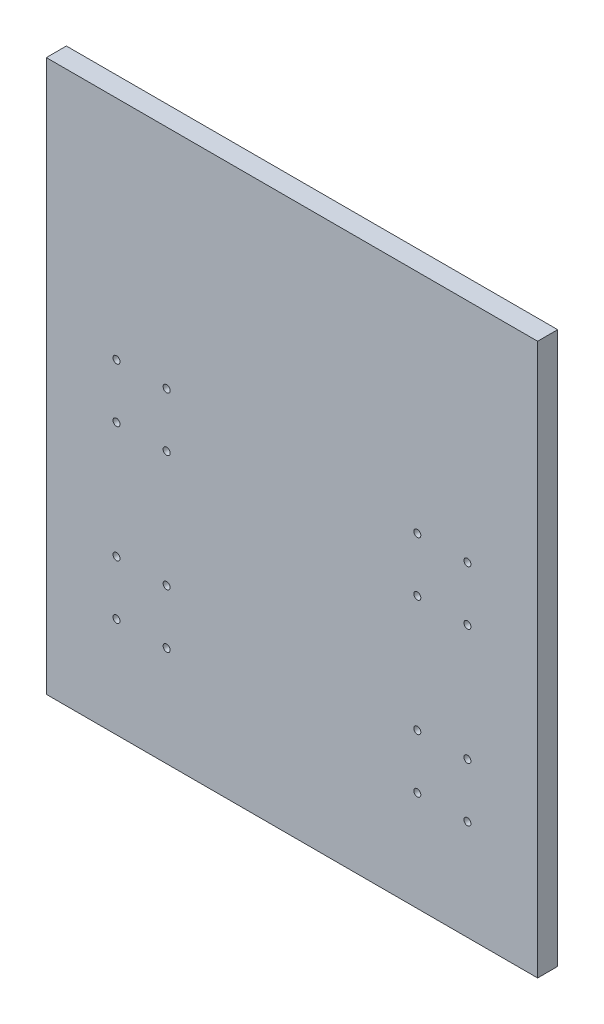
SolidWorks part; units mm, degrees
material "Органическое стекло СО-95-К ГОСТ 10667-90"
ref_plane "Спереди" through (0, 0, 0) normal (0, 0, 1) x (1, 0, 0)
ref_plane "Сверху" through (0, 0, 0) normal (0, 1, 0) x (1, 0, 0)
ref_plane "Справа" through (0, 0, 0) normal (1, 0, 0) x (0, 0, -1)
ref_axis "ОсьX" through (-88.99, 0, 0) along (1, 0, 0)
ref_axis "ОсьZ" through (0, 55, 0) along (0, -1, 0)
ref_axis "ОсьY" through (0, 0, -88.99) along (0, 0, 1)
sketch "Эскиз1" plane through (0, 0, 0) normal (0, 0, 1) x (1, 0, 0)
  line L0 (-150, -2.2268) -> (-150, -90.3848) construction
  line L1 (-245, 275) -> (245, 275)
  line L2 (-245, 275) -> (-245, -275)
  line L3 (-245, -275) -> (245, -275)
  line L4 (245, 275) -> (245, -275)
  line L5 (0, 65.4162) -> (0, -65.4075) construction
  line L6 (-245, 275) -> (-245, -275)
  line L7 (245, 275) -> (245, -275)
  line L8 (-159.2536, -63) -> (189.9089, -63) construction
  circle A0 centre (-175, 49) radius 3.5
  circle A1 centre (-175, -5) radius 3.5
  circle A2 centre (-125, -5) radius 3.5
  circle A3 centre (-125, 49) radius 3.5
  circle A4 centre (125, 49) radius 3.5
  circle A5 centre (125, -5) radius 3.5
  circle A6 centre (175, -5) radius 3.5
  circle A7 centre (175, 49) radius 3.5
  circle A8 centre (-175, -121) radius 3.5
  circle A9 centre (-175, -175) radius 3.5
  circle A10 centre (-125, -175) radius 3.5
  circle A11 centre (-125, -121) radius 3.5
  circle A12 centre (125, -121) radius 3.5
  circle A13 centre (125, -175) radius 3.5
  circle A14 centre (175, -175) radius 3.5
  circle A15 centre (175, -121) radius 3.5
  point P4 (0, 275)
  point P6 (-245, 0)
  dimension "D3" = 7
  dimension "D4" = 54
  dimension "D5" = 50
  dimension "D1" = 490
  dimension "D2" = 550
  dimension "D6" = 300
  dimension "D7" = 170
  dimension "D8" = 100
extrude "Бобышка-Вытянуть1" add sketch "Эскиз1" along normal blind 20 contours L4 L1 L2 L3 A15 A14 A12 A11 A10 A8 A6 A5 A4 A2 A1 A0 A3 A7 A9 A13 region at (0, 0.1443, 0)
